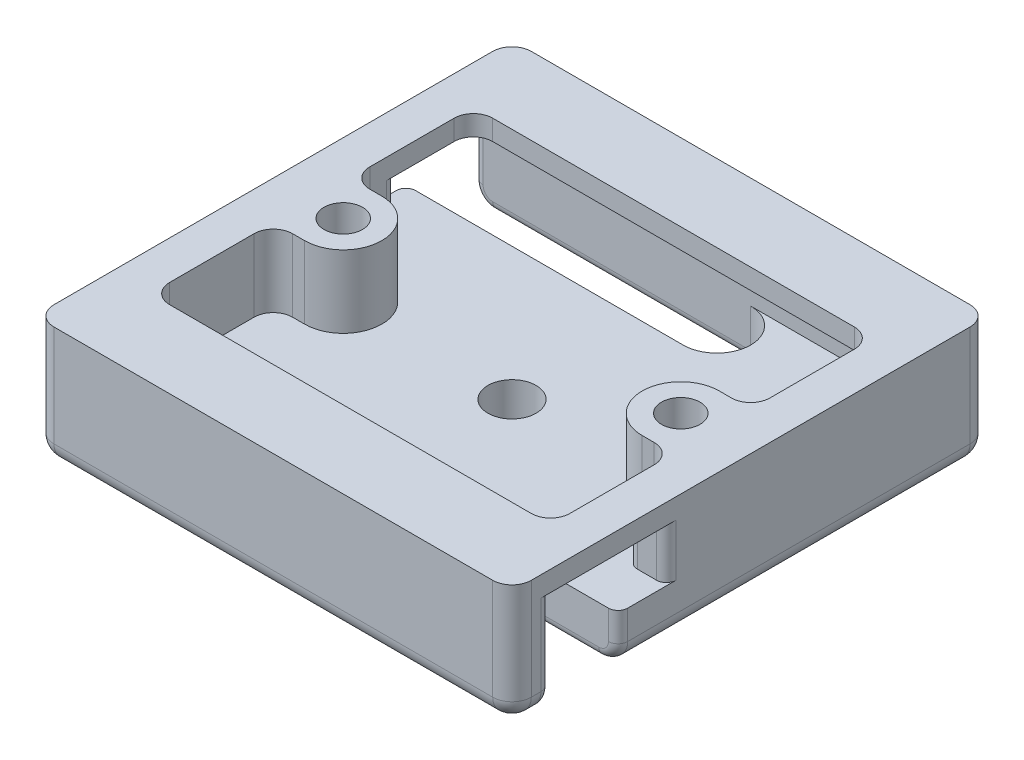
SolidWorks part; units mm, degrees
ref_plane "Alzado" through (0, 0, 0) normal (0, 0, 1) x (1, 0, 0)
ref_plane "Planta" through (0, 0, 0) normal (0, 1, 0) x (1, 0, 0)
ref_plane "Vista lateral" through (0, 0, 0) normal (1, 0, 0) x (0, 0, -1)
sketch "Croquis1" plane through (0, 0, 0) normal (0, 1, 0) x (1, 0, 0)
  line L0 (24.75, -17.25) -> (-4, -17.25) construction
  line L1 (-18.5, -18.5) -> (18.5, -18.5) construction
  line L2 (-18.5, -18.5) -> (-18.5, 18.5) construction
  line L3 (-18.5, 18.5) -> (18.5, 18.5) construction
  line L4 (18.5, -18.5) -> (18.5, 18.5) construction
  line L5 (-18.5, -18.5) -> (18.5, 18.5) construction
  line L6 (-18.5, 18.5) -> (18.5, -18.5) construction
  line L7 (-20.75, -20.75) -> (20.75, -20.75) construction
  line L8 (-20.75, -20.75) -> (-20.75, 20.75) construction
  line L9 (-20.75, 20.75) -> (20.75, 20.75) construction
  line L10 (20.75, -20.75) -> (20.75, 20.75) construction
  line L11 (-20.75, -20.75) -> (20.75, 20.75) construction
  line L12 (-20.75, 20.75) -> (20.75, -20.75) construction
  line L13 (-24.75, -24.75) -> (24.75, -24.75)
  line L14 (-24.75, -24.75) -> (-24.75, 24.75)
  line L15 (-24.75, 24.75) -> (24.75, 24.75)
  line L16 (24.75, -24.75) -> (24.75, 24.75)
  line L17 (-24.75, -24.75) -> (24.75, 24.75) construction
  line L18 (-24.75, 24.75) -> (24.75, -24.75) construction
  line L19 (24.75, -20.75) -> (-4, -20.75)
  line L20 (24.75, -13.75) -> (-4, -13.75)
  line L21 (-7.5, 0) -> (-7.5, -17.25) construction
  line L22 (-24.75, 17.25) -> (4, 17.25) construction
  line L23 (-24.75, 20.75) -> (4, 20.75)
  line L24 (-24.75, 13.75) -> (4, 13.75)
  line L25 (7.5, 17.25) -> (7.5, 0) construction
  line L26 (-4, -20.75) -> (-20.75, -20.75)
  line L27 (-20.75, -20.75) -> (-20.75, 8.75)
  line L28 (4, 20.75) -> (20.75, 20.75)
  line L29 (20.75, 20.75) -> (20.75, -8.75)
  line L30 (-20.75, 8.75) -> (-24.75, 8.75)
  line L31 (20.75, -8.75) -> (24.75, -8.75)
  circle A0 centre (0, 0) radius 7.5 construction
  arc A1 (24.75, -20.75) -> (24.75, -13.75) centre (24.75, -17.25) ccw
  arc A2 (-4, -13.75) -> (-4, -20.75) centre (-4, -17.25) ccw
  arc A3 (-24.75, 20.75) -> (-24.75, 13.75) centre (-24.75, 17.25) ccw
  arc A4 (4, 13.75) -> (4, 20.75) centre (4, 17.25) ccw
  circle A5 centre (0, 0) radius 2.5
  point P0 (0, 0)
  point P5 (0, 0)
  point P19 (10.375, -17.25)
  point P28 (-10.375, 17.25)
  dimension "D7" = 3.5
  dimension "D8" = 15
  dimension "D12" = 5
  dimension "D1" = 37
  dimension "D2" = 37
  dimension "D3" = 2.25
  dimension "D4" = 2.25
  dimension "D10" = 5
  dimension "D11" = 5
  dimension "D5" = 4
  dimension "D6" = 49.5
  dimension "D9" = 4
extrude "Saliente-Extruir1" add sketch "Croquis1" against normal blind 5 contours L27 L30 L14 L13 L16 L19 L26 | A4 L24 L14 L30 L27 L26 A2 L20 L16 L31 L29 L28 A0 | L29 L31 L16 L15 L14 L23 L28 region at (-24.1523, 0, 8) region at (-24.1041, 0, -11.25) region at (-24.1523, 0, -22.75)
extrude "Saliente-Extruir2" add sketch "Croquis1<3>" along normal blind 5.5 contours L27 L30 L14 L13 L16 L19 L26 | L29 L31 L16 L15 L14 L23 L28 region at (-24.1523, 0, 8) region at (-24.1523, 0, -22.75)
sketch "Croquis1<3>" plane through (0, 0, 0) normal (0, 1, 0) x (1, 0, 0) same geometry as "Croquis1"
sketch "Croquis2" plane through (0, 5.5, 0) normal (0, 1, 0) x (1, 0, 0)
  line L12 (-24.75, 24.75) -> (24.75, 24.75)
  line L33 (24.75, 24.75) -> (24.75, -24.75)
  line L34 (24.75, -24.75) -> (-24.75, -24.75)
  line L35 (-24.75, -24.75) -> (-24.75, 24.75)
  line L37 (-20.75, -20.75) -> (-20.75, 8.75) construction
  line L38 (-20.75, -24.75) -> (-20.75, 24.75)
  line L40 (20.75, 24.75) -> (20.75, -24.75)
  line L41 (20.75, 20.75) -> (20.75, -8.75) construction
  line L42 (-20.75, 16.75) -> (20.75, 16.75)
  line L43 (20.75, -16.75) -> (-20.75, -16.75)
  line L44 (24.75, -20.75) -> (-20.75, -20.75) construction
  line L45 (-24.75, 20.75) -> (20.75, 20.75) construction
  line M9 (-20.75, -20.75) -> (-20.75, 8.75)
  line M10 (-20.75, 8.75) -> (-24.75, 8.75)
  line M11 (-24.75, 8.75) -> (-24.75, -24.75)
  line M12 (-24.75, -24.75) -> (24.75, -24.75)
  line M13 (24.75, -24.75) -> (24.75, -20.75)
  line M14 (24.75, -20.75) -> (-20.75, -20.75)
  dimension "D1" = 4
  dimension "D2" = 4
extrude "Saliente-Extruir5" add sketch "Croquis2" along normal blind 2 and the other way blind 0.1 contours L38 L42 L40 L12 | L38 L12 L35 M10 | L40 L43 M9 M14 | L40 L38 L34 M14 | L38 M12 M9 M10 M11 | L12 L40 L33 M14 | L40 M14 M12 M13 region at (-22.75, 5.5, -16.75) region at (0, 5.5, -20.75) region at (-22.75, 5.5, 8) region at (22.75, 5.5, -2) region at (0, 5.5, 22.75) region at (0, 5.5, 18.75) region at (22.75, 5.5, 22.75)
sketch "Croquis3" plane through (0, 7.5, 0) normal (0, 1, 0) x (1, 0, 0)
  line L0 (-24.75, -24.75) -> (-24.75, 24.75) construction
  line L1 (-24.75, -4) -> (-17.5, -4)
  line L2 (-24.75, -4) -> (-24.75, 4)
  line L3 (-24.75, 4) -> (-17.5, 4)
  line L4 (-17.5, -4) -> (-17.5, 4)
  line L5 (0, 24.75) -> (0, -24.75) construction
  line L6 (-24.75, 24.75) -> (24.75, 24.75) construction
  line L7 (-24.75, -24.75) -> (24.75, -24.75) construction
  line L8 (-24.75, 0) -> (20.75, 0) construction
  line L9 (20.75, 20.75) -> (20.75, -8.75) construction
  arc A0 (-17.5, 4) -> (-17.5, -4) centre (-17.5, 0) cw
  circle A1 centre (-17.5, 0) radius 2
  point P19 (-13.5, 0)
  line M7 (-20.75, -16.75) -> (-20.75, 16.75)
  line M10 (-24.75, 24.75) -> (-24.75, -24.75)
  dimension "D3" = 4
  dimension "D2" = 4
  dimension "D1" = 17.5
extrude "Saliente-Extruir6" add sketch "Croquis3" against normal up to surface (7.5 mm away) contours L3 L1 M10 M7 | A1 L4 L3 L1 M7 | A1 L4 A0 region at (-22.75, 7.5, 0) region at (-20.6637, 7.5, 0) region at (-17.4106, 7.5, 3) up to face at (0, 0, 2.5)
extrude "Cortar-Extruir1" cut sketch "Croquis3<3>" against normal up to next contours A1
sketch "Croquis3<3>" plane through (0, 7.5, 0) normal (0, 1, 0) x (1, 0, 0) same geometry as "Croquis3"
mirror "Simetría1" about plane through (0, 0, 0) normal (1, 0, 0) of "Saliente-Extruir6", "Cortar-Extruir1"
sketch "Croquis4" plane through (0, -5, 0) normal (0, -1, 0) x (1, 0, 0)
  circle A0 centre (17.5, 0) radius 2 construction
  circle A1 centre (-17.5, 0) radius 2 construction
  circle A2 centre (17.5, 0) radius 2
  circle A3 centre (-17.5, 0) radius 2
  circle A4 centre (-17.5, 0) radius 3.5
  circle A5 centre (17.5, 0) radius 3.5
  dimension "D1" = 1.5
  dimension "D2" = 1.5
  dimension "D4" = 7
  dimension "D5" = 4
  dimension "D3" = 35
extrude "Cortar-Extruir2" cut sketch "Croquis4" against normal blind 3
fillet "Redondeo1" radius 2 8 edges at (-20.75, 3.75, -4) (-20.75, 3.75, 4) (20.75, 3.75, 4) (20.75, 3.75, -4) (20.75, 6.45, -16.75) (-20.75, 6.45, 16.75) (-20.75, 6.45, -16.75) (20.75, 6.45, 16.75)
fillet "Redondeo4" radius 2 12 edges at (-24.75, 1.25, -24.75) (24.75, 1.25, -24.75) (-24.75, 1.25, 24.75) (24.75, 1.25, 24.75) (20.75, 2.7, -20.75) (-20.75, 2.7, 20.75) (24.75, -5, -5.5) (24.75, -5, 22.75) (0, -5, 24.75) (-24.75, -5, 5.5) (-24.75, -5, -22.75) (0, -5, -24.75)
fillet "Redondeo3" radius 1 18 edges at (20.75, 2.7, 8.75) (24.75, 2.7, 8.75) (24.75, -1.5, 13.75) (-24.75, -1.5, -13.75) (-24.75, 2.7, -8.75) (-20.75, 2.7, -8.75) (24.75, 1.2, 20.75) (-24.75, 1.2, -20.75) (-24.1642, -4.4142, -20.75) (-9.375, -5, -20.75) (7.5, -5, -17.25) (-9.375, -5, -13.75) (-24.1642, -4.4142, -13.75) (24.1642, -4.4142, 20.75) (9.375, -5, 20.75) (-7.5, -5, 17.25) (9.375, -5, 13.75) (24.1642, -4.4142, 13.75)
equation "\"D2@Croquis1\"=\"D1@Croquis1\""
equation "\"D9@Croquis1\"=\"D5@Croquis1\""
